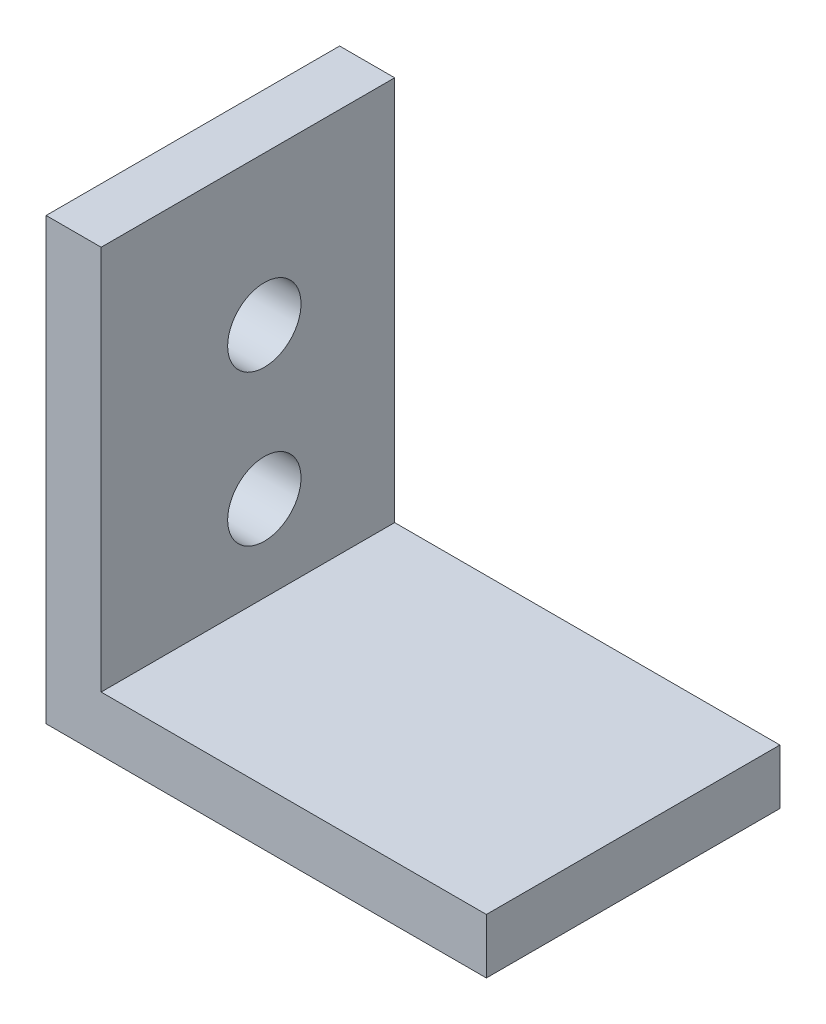
SolidWorks part; units mm, degrees
material "6061 Alloy"
ref_plane "Front Plane" through (0, 0, 0) normal (0, 0, 1) x (1, 0, 0)
ref_plane "Top Plane" through (0, 0, 0) normal (0, 1, 0) x (1, 0, 0)
ref_plane "Right Plane" through (0, 0, 0) normal (1, 0, 0) x (0, 0, -1)
sketch "Sketch1" plane through (0, 0, 0) normal (0, 0, 1) x (1, 0, 0)
  line L0 (-23.7711, 18.9433) -> (-23.7711, -19.1567)
  line L1 (-23.7711, -19.1567) -> (14.3289, -19.1567)
  line L2 (-19.0086, 18.9433) -> (-19.0086, -14.3942)
  line L3 (-19.0086, -14.3942) -> (14.3289, -14.3942)
  line L4 (-23.7711, 18.9433) -> (-19.0086, 18.9433)
  line L5 (14.3289, -14.3942) -> (14.3289, -19.1567)
  dimension "D1" = 38.1
  dimension "D2" = 38.1
  dimension "D3" = 4.7625
extrude "Boss-Extrude1" add sketch "Sketch1" along normal blind 25.4
sketch "Sketch2" plane through (-23.7711, 0, 0) normal (-1, 0, 0) x (0, 0, 1)
  circle A0 centre (11.2779, 6.0592) radius 3.175
  circle A1 centre (11.2779, -6.9755) radius 3.175
  dimension "D1" = 6.35
extrude "Cut-Extrude1" cut sketch "Sketch2" against normal up to next
